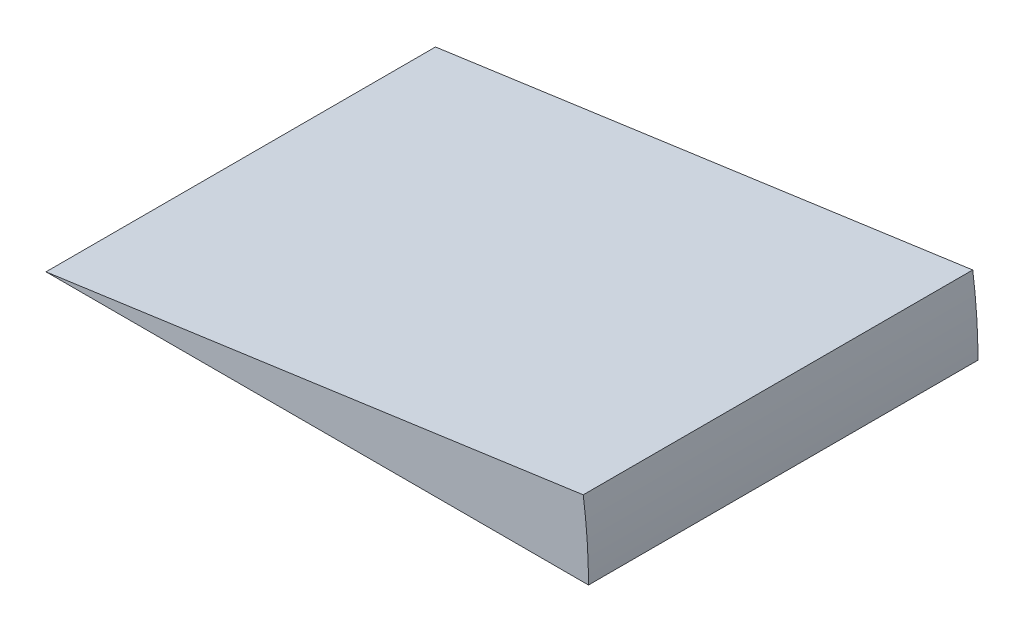
SolidWorks part; units mm, degrees
ref_plane "Front Plane" through (0, 0, 0) normal (0, 0, 1) x (1, 0, 0)
ref_plane "Top Plane" through (0, 0, 0) normal (0, 1, 0) x (1, 0, 0)
ref_plane "Right Plane" through (0, 0, 0) normal (1, 0, 0) x (0, 0, -1)
sketch "Sketch1" plane through (0, 0, 0) normal (0, 1, 0) x (1, 0, 0)
  line L1 (-54.483, -39.116) -> (54.483, -39.116)
  line L2 (-54.483, -39.116) -> (-54.483, 39.116)
  line L3 (-54.483, 39.116) -> (54.483, 39.116)
  line L4 (54.483, -39.116) -> (54.483, 39.116)
  line L5 (-54.483, -39.116) -> (54.483, 39.116) construction
  line L6 (-54.483, 39.116) -> (54.483, -39.116) construction
  point P0 (0, 0)
  dimension "D1" = 108.966
  dimension "D2" = 78.232
revolve "Revolve1" add sketch "Sketch1" angle 8 about L2 reverse direction yes
